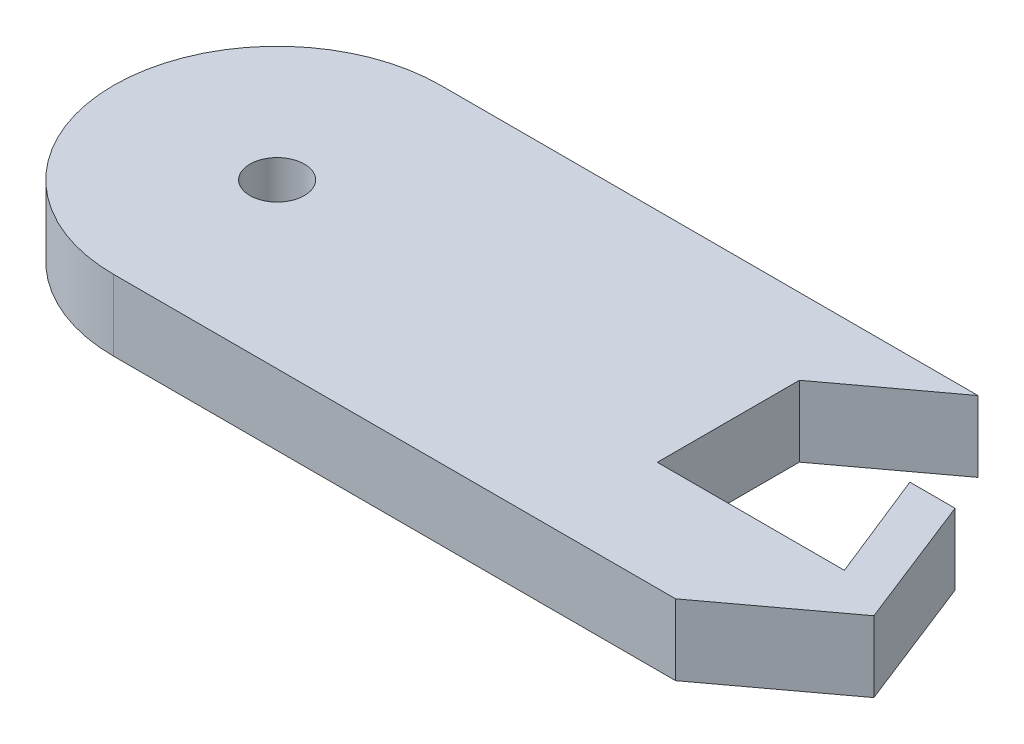
SolidWorks part; units mm, degrees
ref_plane "Front Plane" through (0, 0, 0) normal (0, 0, 1) x (1, 0, 0)
ref_plane "Top Plane" through (0, 0, 0) normal (0, 1, 0) x (1, 0, 0)
ref_plane "Right Plane" through (0, 0, 0) normal (1, 0, 0) x (0, 0, -1)
sketch "Sketch1" plane through (0, 0, 0) normal (0, 1, 0) x (1, 0, 0)
  line L1 (0, 0) -> (80, 0)
  line L2 (0, 0) -> (0, 30)
  line L3 (0, 30) -> (80, 30)
  line L4 (80, 0) -> (80, 30)
  dimension "D1" = 30
  dimension "D2" = 80
extrude "Boss-Extrude1" add sketch "Sketch1" along normal blind 6.5
fillet "Fillet1" radius 15 2 edges at (0, 3.25, 0) (0, 3.25, -30)
sketch "Sketch2" plane through (0, 6.5, 0) normal (0, 1, 0) x (1, 0, 0)
  line L0 (80, 30) -> (15, 30) construction
  circle A0 centre (15, 15) radius 2.5
  dimension "D1" = 5
  dimension "D2" = 15
  dimension "D3" = 15
extrude "Cut-Extrude1" cut sketch "Sketch2" against normal up to next
sketch "Sketch3" plane through (0, 6.5, 0) normal (0, 1, 0) x (1, 0, 0)
  line L0 (68, 20) -> (72, 10)
  line L1 (72, 10) -> (54.8504, 10)
  line L2 (54.8504, 10) -> (54.8504, 23.0255)
  line L3 (54.8504, 23.0255) -> (64.2482, 30)
  line L4 (80, 30) -> (15, 30) construction
  line L5 (64.2482, 30) -> (80, 30)
  line L6 (80, 30) -> (80, 20)
  line L8 (68, 20) -> (80, 20)
  line L9 (15, 0) -> (80, 0) construction
  line L10 (80, 0) -> (80, 30) construction
  dimension "D1" = 10
  dimension "D2" = 10
  dimension "D3" = 12
  dimension "D4" = 8
extrude "Cut-Extrude2" cut sketch "Sketch3" against normal through all
sketch "Sketch4" plane through (0, 6.5, 0) normal (0, 1, 0) x (1, 0, 0)
  line L0 (80, 20) -> (80, 0)
  line L1 (80, 0) -> (72.1472, 20)
  line L2 (68, 20) -> (80, 20) construction
  line L3 (72.1472, 20) -> (80, 20)
extrude "Cut-Extrude3" cut sketch "Sketch4" against normal up to next
sketch "Sketch5" plane through (0, 6.5, 0) normal (0, 1, 0) x (1, 0, 0)
  line L1 (80, 0) -> (80, 10)
  line L2 (80, 10) -> (66.5254, 0)
  line L3 (15, 0) -> (80, 0) construction
  line L4 (66.5254, 0) -> (80, 0)
extrude "Cut-Extrude4" cut sketch "Sketch5" against normal through all
